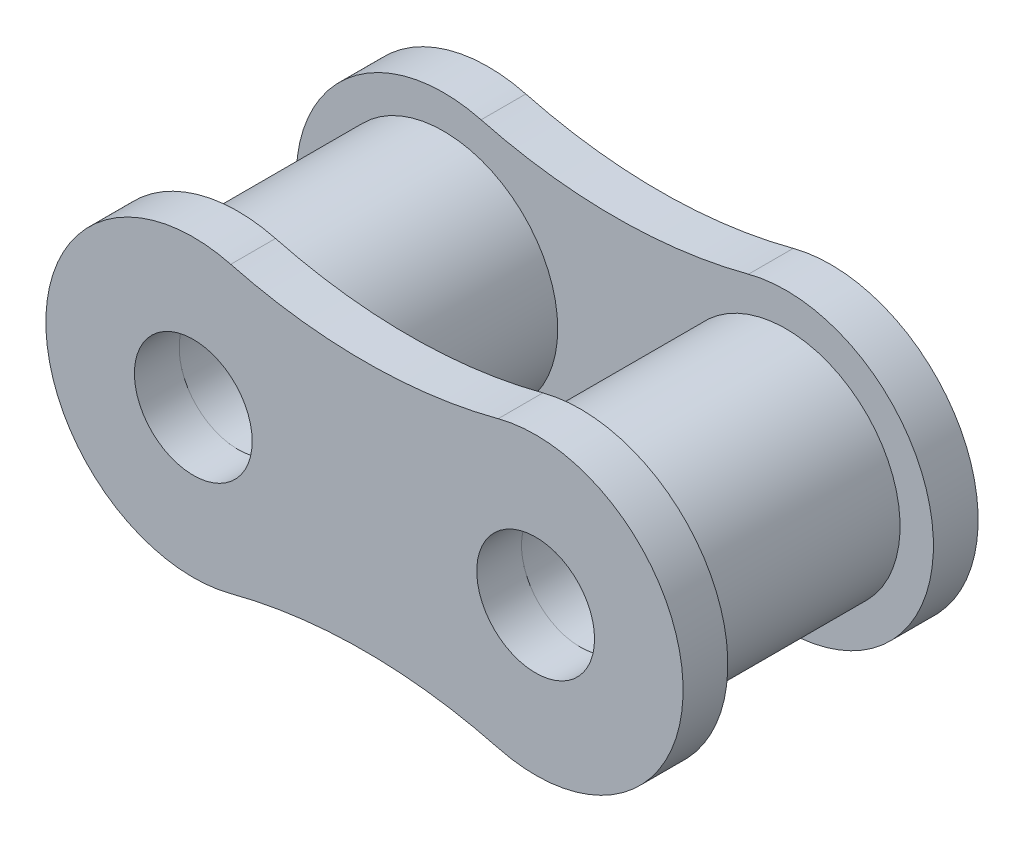
SolidWorks part; units mm, degrees
material "1023 Carbon Steel Sheet (SS)"
ref_plane "Front Plane" through (0, 0, 0) normal (0, 0, 1) x (1, 0, 0)
ref_plane "Top Plane" through (0, 0, 0) normal (0, 1, 0) x (1, 0, 0)
ref_plane "Right Plane" through (0, 0, 0) normal (1, 0, 0) x (0, 0, -1)
sketch "Sketch1" plane through (0, 0, 0) normal (0, 0, 1) x (1, 0, 0)
  line L0 (-4.7625, 0) -> (4.7625, 0) construction
  line L1 (-4.7625, 4.1021) -> (-4.7625, -4.1021) construction
  line L2 (0, -3.4868) -> (0, 3.4868) construction
  circle A0 centre (-4.7625, 0) radius 3.175
  circle A1 centre (4.7625, 0) radius 3.175
  circle A2 centre (-4.7625, 0) radius 1.6383
  circle A3 centre (4.7625, 0) radius 1.6383
  arc A4 (-3.7199, 3.9674) -> (-3.7199, -3.9674) centre (-4.7625, 0) ccw
  arc A5 (3.7199, -3.9674) -> (3.7199, 3.9674) centre (4.7625, 0) ccw
  arc A6 (-3.7199, 3.9674) -> (3.7199, 3.9674) centre (0, 18.1231) ccw
  arc A7 (-3.7199, -3.9674) -> (3.7199, -3.9674) centre (0, -18.1231) cw
  dimension "Roller Dia" = 6.35
  dimension "Pin Dia" = 3.2766
  dimension "Pitch" = 9.525
  dimension "H" = 8.2042
  dimension "D2" = 6.9736
sketch "Sketch2" plane through (0, 0, 0) normal (0, 1, 0) x (1, 0, 0)
  line L0 (0, 2.86) -> (0, -2.86) construction
  point P2 (0, -4.1046)
  point P4 (0, 4.1046)
  point P5 (0, 4.1554)
  point P6 (0, 5.146)
  dimension "W" = 5.72
  dimension "T" = 1.2446
  dimension "D1" = 1.2446
  dimension "T1" = 0.9906
  dimension "D3" = 0.0508
ref_plane "Plane1" through (0, 0, 2.86) normal (0, 0, 1) x (1, 0, 0)
ref_plane "Plane2" through (0, 0, -4.1554) normal (0, 0, 1) x (1, 0, 0)
sketch "Sketch4" plane through (0, 0, 0) normal (0, 0, 1) x (1, 0, 0)
  circle A0 centre (-4.7625, 0) radius 3.175 construction
  circle A1 centre (-4.7625, 0) radius 3.175
  circle A2 centre (4.7625, 0) radius 3.175 construction
  circle A3 centre (4.7625, 0) radius 3.175
  circle A4 centre (-4.7625, 0) radius 1.6637
  circle A5 centre (4.7625, 0) radius 1.6637
  dimension "D1" = 3.3274
  dimension "D2" = 3.3274
extrude "Boss-Extrude1" add sketch "Sketch4" along normal mid plane 5.72
sketch "Sketch5" plane through (0, 0, 2.86) normal (0, 0, 1) x (1, 0, 0)
  arc A0 (-3.7199, 3.9674) -> (-3.7199, -3.9674) centre (-4.7625, 0) ccw construction
  arc A1 (-3.7199, 3.9674) -> (3.7199, 3.9674) centre (0, 18.1231) ccw construction
  circle A2 centre (-4.7625, 0) radius 1.6383 construction
  arc A3 (3.7199, -3.9674) -> (3.7199, 3.9674) centre (4.7625, 0) ccw construction
  circle A4 centre (4.7625, 0) radius 1.6383 construction
  arc A5 (3.7199, -3.9674) -> (-3.7199, -3.9674) centre (0, -18.1231) ccw construction
  arc A6 (-3.7199, 3.9674) -> (-3.7199, -3.9674) centre (-4.7625, 0) ccw
  arc A7 (-3.7199, 3.9674) -> (3.7199, 3.9674) centre (0, 18.1231) ccw
  circle A8 centre (-4.7625, 0) radius 1.6383
  arc A9 (3.7199, -3.9674) -> (3.7199, 3.9674) centre (4.7625, 0) ccw
  circle A10 centre (4.7625, 0) radius 1.6383
  arc A11 (3.7199, -3.9674) -> (-3.7199, -3.9674) centre (0, -18.1231) ccw
extrude "Boss-Extrude2" add sketch "Sketch5" along normal up to vertex (1.2446 mm away) separate body up to point (0, 0, 4.1046)
mirror "Mirror2" about plane through (0, 0, 0) normal (0, 0, 1) of "Boss-Extrude2"
equation "\"D2@Sketch1\" =\"H@Sketch1\"*.85"
equation "\"D1@Sketch2\" = \"T@Sketch2\""
equation "\"D1@Sketch4\" = \"Pin Dia@Sketch1\"+.002"
equation "\"D2@Sketch4\" = \"D1@Sketch4\""
equation "\"D1@Boss-Extrude1\" = \"W@Sketch2\""
